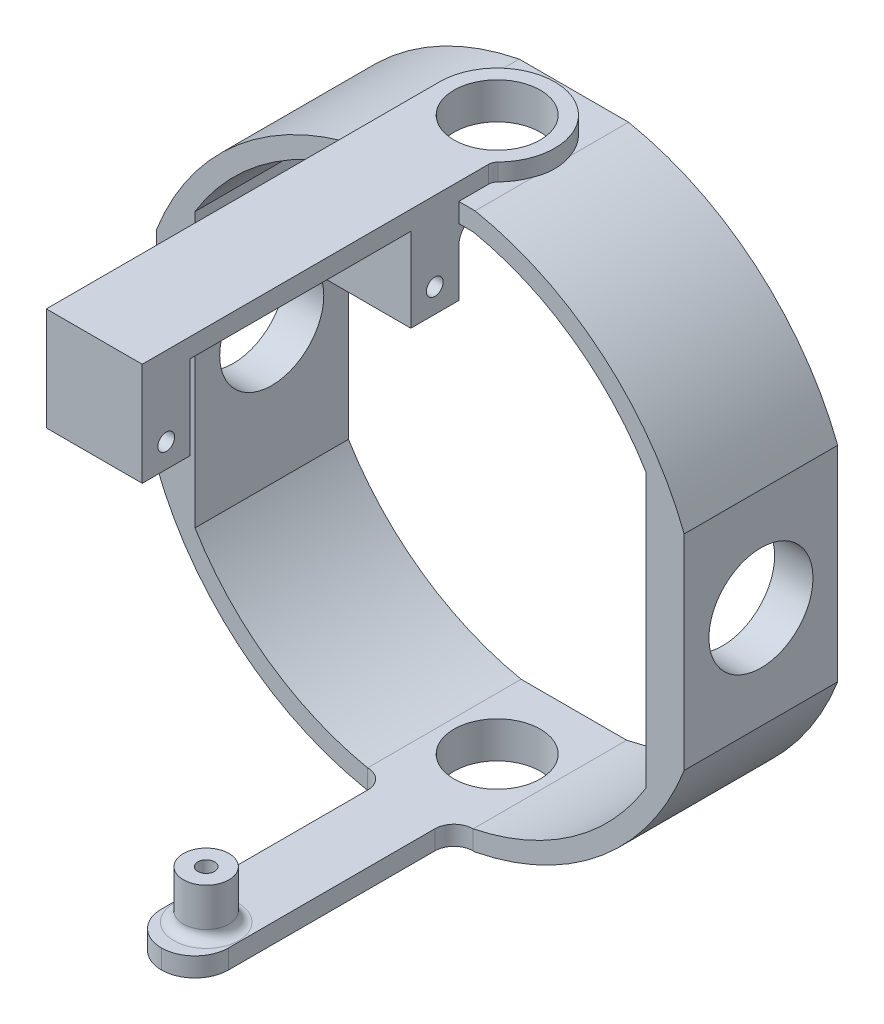
SolidWorks part; units mm, degrees
note: '?' marks a value the reader was unsure of.
ref_plane "Front Plane" through (0, 0, 0) normal (1, 0, 0) x (0, 1, 0)
ref_plane "Top Plane" through (0, 0, 0) normal (0, 0, 1) x (0, 1, 0)
ref_plane "Right Plane" through (0, 0, 0) normal (0, 1, 0) x (-1, 0, 0)
sketch "Sketch2" plane through (0, 0, 0) normal (0, 0, 1) x (0, 1, 0)
  line L0 (-10.2956, 25.5) -> (10.2956, 25.5)
  line L1 (-10.6771, 27.5) -> (10.6771, 27.5)
  line L2 (10.2956, -25.5) -> (-10.2956, -25.5)
  line L3 (-26.9444, 5.5) -> (-26.9444, -5.5)
  line L4 (-28.9444, 5.6985) -> (-28.9444, -5.6985)
  line L5 (26.9444, 5.5) -> (26.9444, -5.5)
  line L6 (28.9444, -5.6985) -> (28.9444, 5.6985)
  line L7 (10.6771, -27.5) -> (-10.6771, -27.5)
  line L8 (-14.2829, 23.5) -> (14.2829, 23.5)
  line L9 (-14.2829, -23.5) -> (14.2829, -23.5)
  arc A0 (-26.9444, -5.5) -> (-10.2956, -25.5) centre (0, 0) ccw
  arc A1 (-28.9444, -5.6985) -> (-10.6771, -27.5) centre (0, 0) ccw
  circle A2 centre (0, 0) radius 28.5 construction
  arc A3 (26.9444, 5.5) -> (10.2956, 25.5) centre (0, 0) ccw
  arc A4 (28.9444, 5.6985) -> (10.6771, 27.5) centre (0, 0) ccw
  arc A5 (-10.2956, 25.5) -> (-26.9444, 5.5) centre (0, 0) ccw
  arc A6 (-10.6771, 27.5) -> (-28.9444, 5.6985) centre (0, 0) ccw
  arc A7 (10.6771, -27.5) -> (28.9444, -5.6985) centre (0, 0) ccw
  arc A8 (10.2956, -25.5) -> (26.9444, -5.5) centre (0, 0) ccw
  point P5 (27.5, 0)
  point P7 (28.5, 0)
  dimension "D1" = 2
  dimension "D2" = 57
  dimension "D3" = 2
  dimension "D6" = 1
  dimension "D4" = 11
  dimension "D5" = 2
  dimension "D7" = 2
  dimension "D8" = 2
  dimension "D9" = 2
extrude "Boss-Extrude1" add sketch "Sketch2" along normal blind 16 contours L0 A5 L8 A3 | L7 A7 L6 A4 L1 A6 L4 A1 A8 L2 A0 L3 A5 L0 A3 L5 | L2 A8 L9 A0
sketch "Sketch3" plane through (0, 0, 16) normal (0, 0, 1) x (1, 0, 0)
  line L5 (-3.5, -26.9444) -> (-3.5, -28.9444)
  line L6 (-3.5, -28.9444) -> (3.5, -28.9444)
  line L7 (3.5, -28.9444) -> (3.5, -26.9444)
  line L8 (3.5, -26.9444) -> (-3.5, -26.9444)
  line L13 (-5.5, -26.9444) -> (5.5, -26.9444) construction
  line L14 (-5.6985, -28.9444) -> (5.6985, -28.9444) construction
  point P34 (0, -28.9444)
  dimension "D1" = 7
extrude "Boss-Extrude2" add sketch "Sketch3" along normal blind 27
fillet "Fillet1" radius 3.5 2 edges at (-3.5, -27.9444, 43) (3.5, -27.9444, 43)
sketch "Sketch4" plane through (0, 0, 0) normal (1, 0, 0) x (0, 1, 0)
  line L0 (0, 0) -> (0, 8) construction
  line L1 (0, 8) -> (0, 16) construction
  line L3 (10.6771, 16) -> (-10.6771, 16) construction
  circle A0 centre (0, 8) radius 5.425
  dimension "D1" = 10.85
extrude "Cut-Extrude1" cut sketch "Sketch4" against normal through all both and the other way through all
sketch "Sketch5" plane through (0, 0, 0) normal (0, 1, 0) x (-1, 0, 0)
  line L0 (0, 0) -> (0, 8) construction
  line L1 (0, 8) -> (0, 16) construction
  line L4 (-5.6985, 16) -> (5.6985, 16) construction
  circle A0 centre (0, 8) radius 4.5
  circle A1 centre (0, 38.3333) radius 0.875
  dimension "D1" = 9
  dimension "D2" = 1.75
extrude "Cut-Extrude2" cut sketch "Sketch5" against normal through all both and the other way through all
ref_axis "Axis1" [suppressed] through (0, -30.5331, 8) along (0, 1, 0)?
ref_axis "Axis2" through (-28.498, 0, 8) along (1, 0, 0)?
ref_point "Center" [suppressed]
sketch "Sketch8" plane through (0, -28.9444, 0) normal (0, -1, 0) x (1, 0, 0)
  circle A0 centre (0, 8) radius 4.5 construction
  circle A1 centre (0, 8) radius 4.5
  circle A2 centre (0, 8) radius 6
  dimension "D1" = 1.5
extrude "Boss-Extrude4" add sketch "Sketch8" along normal blind 1.8 and the other way up to next
mirror "Mirror1" about plane through (0, 0, 0) normal (0, 1, 0) of "Boss-Extrude4"
fillet "Fillet2" radius 2 2 edges at (-3.5, -27.9444, 16) (3.5, -27.9444, 16)
sketch "Sketch6" plane through (0, 0, 0) normal (1, 0, 0) x (0, 1, 0)
  line L2 (19.9944, 49) -> (19.9944, 44)
  line L3 (19.9944, 44) -> (28.7444, 44)
  line L5 (30.7444, 49) -> (30.7444, 16)
  line L6 (28.9444, 16) -> (19.9944, 16)
  line L7 (19.9944, 16) -> (19.9944, 21)
  line L8 (19.9944, 21) -> (28.7444, 21)
  line L9 (28.7444, 21) -> (28.7444, 44)
  line L16 (19.9944, 49) -> (30.7444, 49)
  line L18 (28.9444, 16) -> (10.6771, 16) construction
  line L19 (30.7444, 2) -> (30.7444, 14) construction
  line L26 (28.9444, 16) -> (28.8834, 8)
  line L27 (28.8834, 8) -> (30.7444, 8)
  line L28 (30.7444, 8) -> (30.7444, 16)
  line L32 (30.7444, 14) -> (28.9444, 14) construction
  circle A0 centre (22.4944, 46.5) radius 0.875
  circle A1 centre (22.4944, 18.5) radius 0.875
  spline S0 degree 2 poles (28.9444, 6.1218) (28.8225, 8) (28.9444, 9.8782) knots 0.297184 0.297184 0.297184 0.610214 0.610214 0.610214 weights 0.027066 0.028944 0.030823 construction
  dimension "D10" = 1.75
  dimension "D16" = 2.5
  dimension "D2" = 6
  dimension "D3" = 5
  dimension "D4" = 2
  dimension "D5" = 5
  dimension "D6" = 23
  dimension "D7" = 2.5
  dimension "D13" = 2.5
  dimension "D14" = 6.25
extrude "Boss-Extrude3" add sketch "Sketch6" along normal blind 4 and the other way blind 6
fillet "Fillet3" radius 2 2 edges at (-5.7502, 26.8921, 16) (-0.75, 26.9444, 16)
sketch "Sketch9" plane through (0, 0, 0) normal (0, 1, 0) x (-1, 0, 0)
  line L0 (0, 0) -> (0, 8) construction
  line L1 (0, 8) -> (0, 16) construction
  line L2 (27.5, 16) -> (6, 16) construction
  circle A0 centre (0, 8) radius 4.5
  dimension "D1" = 9
extrude "Cut-Extrude3" cut sketch "Sketch9" against normal through all both and the other way through all
sketch "Sketch10" plane through (0, -26.9444, 0) normal (0, 1, 0) x (-1, 0, 0)
  circle A0 centre (0, 38.3333) radius 0.875
  circle A1 centre (0, 38.3333) radius 2.375
  circle A2 centre (0, 38.3333) radius 0.875 construction
  dimension "D1" = 1.5
extrude "Boss-Extrude5" add sketch "Sketch10" along normal blind 5
fillet "Fillet4" radius 1 2 edges at (0, -26.9444, 40.7083) (4, 29.8444, 12.4721)
equation "\"motorDiam\"= 40mm"
equation "\"motorHeight\"= 120mm"
